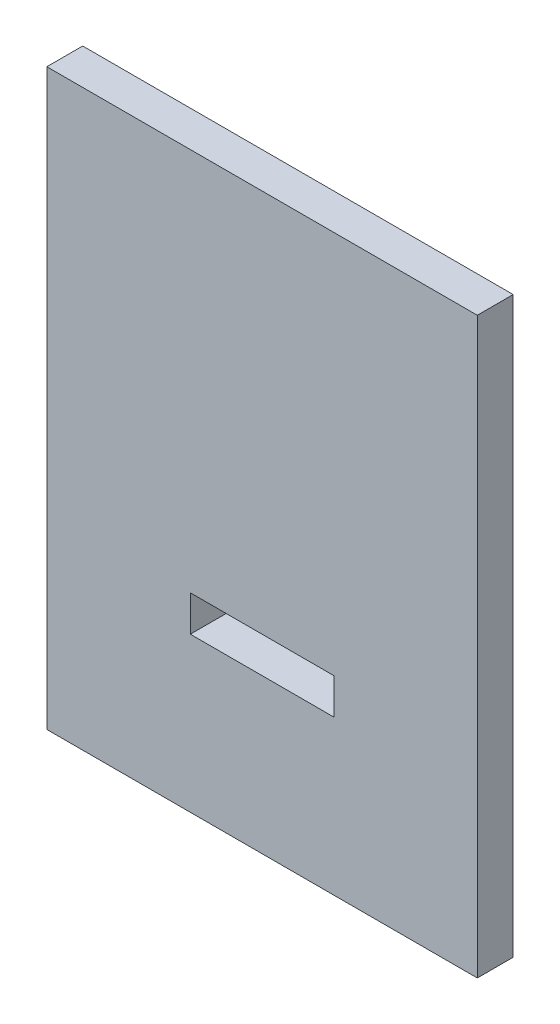
SolidWorks part; units mm, degrees
material "PBT General Purpose"
ref_plane "Front Plane" through (0, 0, 0) normal (0, 0, 1) x (1, 0, 0)
ref_plane "Top Plane" through (0, 0, 0) normal (0, 1, 0) x (1, 0, 0)
ref_plane "Right Plane" through (0, 0, 0) normal (1, 0, 0) x (0, 0, -1)
sketch "frame_outline" plane through (0, 0, 0) normal (0, 0, 1) x (1, 0, 0)
  line L124 (0, 0) -> (3, 0)
  line L125 (0, 0) -> (0, 4)
  line L126 (0, 4) -> (3, 4)
  line L127 (3, 0) -> (3, 4)
  line L132 (1, 1.325) -> (2, 1.325)
  line L133 (1, 1.325) -> (1, 1.075)
  line L134 (1, 1.075) -> (2, 1.075)
  line L135 (2, 1.325) -> (2, 1.075)
  point P4 (1, 1.2)
  point P12 (1.5, 1.075)
  point P13 (1.5, 0)
  dimension "D1" = 1
  dimension "D2" = 3
  dimension "D3" = 0.25
  dimension "D4" = 4
  dimension "D5" = 2.8
extrude "Boss-Extrude1" add sketch "frame_outline" along normal mid plane 0.25
equation "\"t\"= 0.25'thickness of the sheets"
equation "\"t_cf\" = 0.115'thickness of single carbon fiber layer"
equation "\"t_kapton\" = 0.025'thickness of single Kapton flex layer"
equation "\"t_fr4\" = 0.1'thickness of FR4 with copper layer"
equation "\"joint_flex\"= 0.1'Width of flextures gap"
equation "\"joint_flex_eff\"= 0.02'Width of flecture after castelation"
equation "\"joint_fold\"= 0.2'Width of folding joints for 90deg fold"
equation "\"gap_tolerance\"= 0.002'Width to have interfecence fit between carbon fiber inserts"
equation "\"assemble_angle\"= 90'Angle of assembly parts"
equation "\"D1@Boss-Extrude1\"=\"t\""
equation "\"link_lift\"= 0.5'Actuation linkage amplification for the lift motion"
equation "\"link_swing\"= 0.45'Actuation linkage amplification for the swing motion"
equation "\"D3@frame_outline\"=\"t\""
